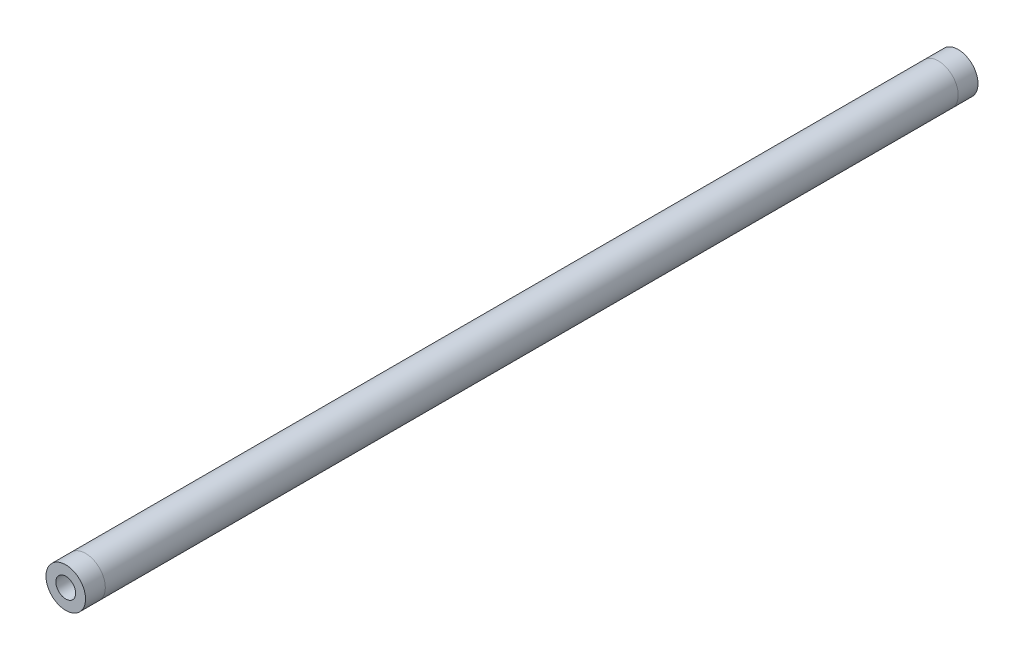
SolidWorks part; units mm, degrees
ref_plane "Front Plane" through (0, 0, 0) normal (0, 0, 1) x (1, 0, 0)
ref_plane "Top Plane" through (0, 0, 0) normal (0, 1, 0) x (1, 0, 0)
ref_plane "Right Plane" through (0, 0, 0) normal (1, 0, 0) x (0, 0, -1)
sketch "Axis" plane through (0, 0, 0) normal (1, 0, 0) x (0, 0, -1)
  line L0 (0, 0) -> (286.4241, 0) construction
  line L1 (286.4241, 0) -> (280.0741, 0)
  line L2 (286.4241, 0) -> (308.3189, 0) construction
  line L3 (0, 0) -> (-21.8948, 0) construction
  point P4 (0, 0)
  point P5 (286.4241, 0)
  point P6 (280.0741, 0)
  dimension "D1" = 6.35
  dimension "D2" = 21.8948
  dimension "D3" = 21.8948
sketch "Sketch1" plane through (0, 0, 0) normal (0, 0, 1) x (1, 0, 0)
  circle A0 centre (0, 0) radius 6.35
  circle A1 centre (0, 0) radius 4.826
  circle A2 centre (0, 0) radius 3.175
  dimension "D1" = 12.7
  dimension "D2" = 1.524
  dimension "D3" = 6.35
extrude "Threaded insert 1-1" add sketch "Sketch1" against normal blind 6.35 contours A0 A1 | A1 A2 region at (-6.1704, 0, 0) region at (-4.6895, 0, 0)
extrude "Threaded insert 1-2" add sketch "Sketch1<3>" against normal blind 9.525 from surface contours A1 A2 region at (-4.6895, 0, 0) starting at face at (6.35, 0, -6.35)
sketch "Sketch1<3>" plane through (0, 0, 0) normal (0, 0, 1) x (1, 0, 0) same geometry as "Sketch1"
extrude "Tube extrude" add sketch "Sketch1<4>" against normal up to vertex (280.0741 mm away) from surface separate body contours A0 A1 region at (-6.1704, 0, 0) up to point (0, 0, -280.0741) starting at face at (4.826, 0, -6.35)
sketch "Sketch1<4>" plane through (0, 0, 0) normal (0, 0, 1) x (1, 0, 0) same geometry as "Sketch1"
extrude "Threaded insert 2-1" add sketch "Sketch1<6>" along normal blind 9.525 from surface separate body contours A1 A2 region at (-4.6895, 0, 0) starting at face at (4.826, 0, -280.0741)
sketch "Sketch1<6>" plane through (0, 0, 0) normal (0, 0, 1) x (1, 0, 0) same geometry as "Sketch1"
extrude "Threaded insert 2-2" add sketch "Sketch1<9>" against normal blind 6.35 from surface separate body contours A1 A2 | A0 A1 region at (-6.1704, 0, 0) region at (-4.6895, 0, 0) starting at face at (4.826, 0, -280.0741)
sketch "Sketch1<9>" plane through (0, 0, 0) normal (0, 0, 1) x (1, 0, 0) same geometry as "Sketch1"
combine bodies "Combine1" operation type add bodies to combine 106 104
equation "\"Threaded insert outer thickness\"= .25"
equation "\"D1@Threaded insert 1-1\"=\"Threaded insert outer thickness\""
equation "\"D1@Threaded insert 2-2\"=\"Threaded insert outer thickness\""
equation "\"D1@Axis\" = \"Threaded insert outer thickness\""
